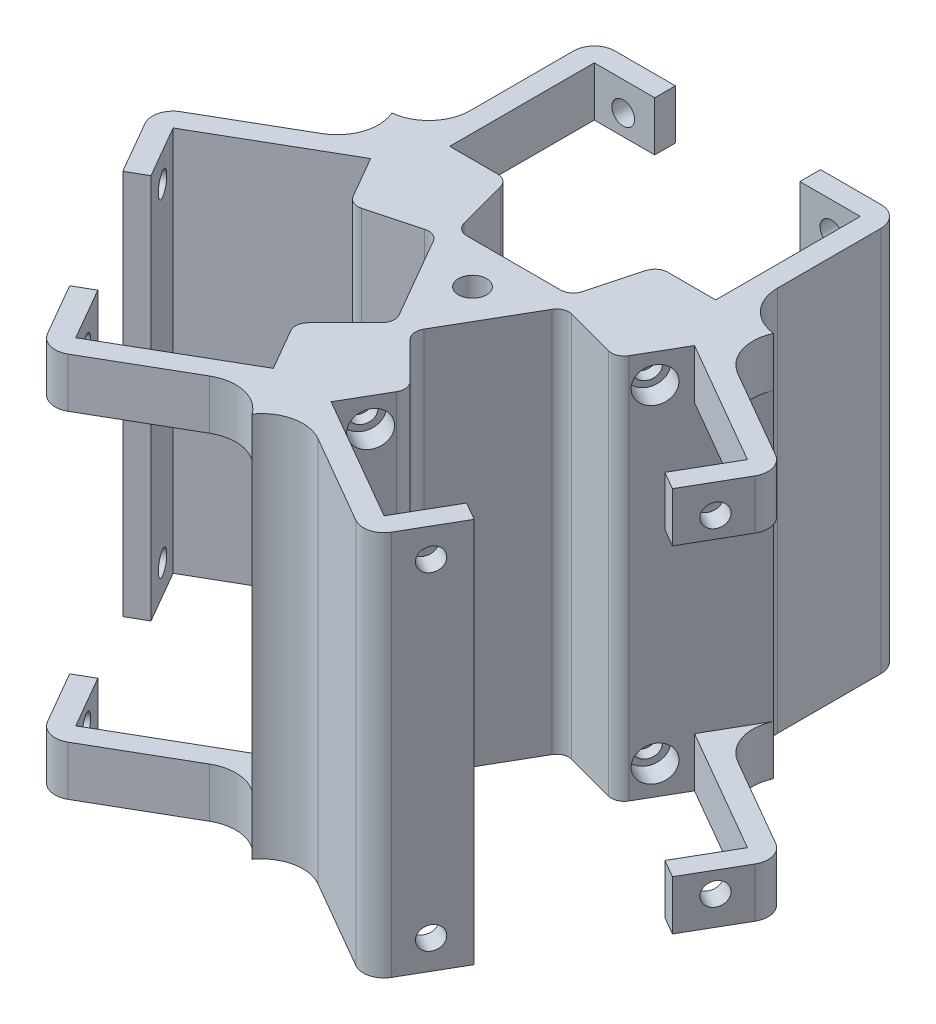
SolidWorks part; units mm, degrees
ref_plane "Alzado" through (0, 0, 0) normal (0, 0, 1) x (1, 0, 0)
ref_plane "Planta" through (0, 0, 0) normal (0, 1, 0) x (1, 0, 0)
ref_plane "Vista lateral" through (0, 0, 0) normal (1, 0, 0) x (0, 0, -1)
sketch "Croquis1" plane through (0, 0, 0) normal (0, 1, 0) x (1, 0, 0)
  line L0 (0, 50.8) -> (0, -50.8) construction
  line L1 (-50.8, 0) -> (50.8, 0) construction
  line L2 (0, 0) -> (-35.921, -35.921) construction
  line L3 (0, 0) -> (35.921, -35.921) construction
  line L10 (0, -17.5) -> (-15.1554, 8.75) construction
  line L11 (-15.1554, 8.75) -> (15.1554, 8.75) construction
  line L12 (15.1554, 8.75) -> (0, -17.5) construction
  line L13 (-1.2978, -16.7522) -> (-15.1813, 7.2027) construction
  line L14 (1.2978, -16.7522) -> (15.1813, 7.2027) construction
  line L15 (-13.8835, 9.4549) -> (13.8835, 9.4549) construction
  line L16 (1.6964, -16.0645) -> (13.335, -27.7031)
  line L17 (13.335, -27.7031) -> (0, -50.8)
  line L18 (0, -50.8) -> (-13.335, -27.7031)
  line L19 (-13.335, -27.7031) -> (-1.6964, -16.0645)
  line L20 (-17.3241, 25.4) -> (-13.0641, 9.5013)
  line L21 (-43.9941, 25.4) -> (-17.3241, 25.4)
  line L22 (-30.6591, 2.3031) -> (-43.9941, 25.4)
  line L23 (-14.7604, 6.5631) -> (-30.6591, 2.3031)
  line L24 (30.6591, 2.3031) -> (14.7604, 6.5631)
  line L25 (43.9941, 25.4) -> (30.6591, 2.3031)
  line L26 (17.3241, 25.4) -> (43.9941, 25.4)
  line L27 (13.0641, 9.5013) -> (17.3241, 25.4)
  line L28 (-14.7604, 6.5631) -> (-1.6964, -16.0645)
  line L29 (1.6964, -16.0645) -> (14.7604, 6.5631)
  line L30 (-13.0641, 9.5013) -> (13.0641, 9.5013)
  line L31 (-43.9941, 25.4) -> (0, -50.8) construction
  line L32 (43.9941, 25.4) -> (0, -50.8) construction
  line L33 (-43.9941, 25.4) -> (43.9941, 25.4) construction
  circle A0 centre (0, 0) radius 50.8 construction
  circle A7 centre (0, 0) radius 17.5 construction
  circle A8 centre (-13.8835, 7.9549) radius 1.5 construction
  circle A9 centre (13.8835, 7.9549) radius 1.5 construction
  circle A10 centre (0, -16) radius 1.5 construction
  arc A11 (-15.1813, 7.2027) -> (-13.8835, 9.4549) centre (-13.8835, 7.9549) cw construction
  arc A12 (15.1813, 7.2027) -> (13.8835, 9.4549) centre (13.8835, 7.9549) ccw construction
  arc A13 (1.2978, -16.7522) -> (-1.2978, -16.7522) centre (0, -16) cw construction
  arc A14 (-15.1813, 7.2027) -> (-13.8835, 9.4549) centre (-13.8835, 7.9549) cw construction
  arc A15 (13.8835, 9.4549) -> (15.1813, 7.2027) centre (13.8835, 7.9549) cw construction
  arc A16 (-1.2978, -16.7522) -> (1.2978, -16.7522) centre (0, -16) ccw construction
  circle A17 centre (0, 0) radius 76.2 construction
  point P45 (0, 0)
  dimension "D1" = 101.6
  dimension "D6" = 13.8835
  dimension "D9" = 3
  dimension "D5" = 3
  dimension "D4" = 35
  dimension "D10" = 152.4
  dimension "D2" = 45
  dimension "D3" = 45
  dimension "D7" = 26.67
extrude "Saliente-Extruir1" add sketch "Croquis1" along normal blind 88.9
sketch "Croquis4" plane through (0, 88.9, 0) normal (0, 1, 0) x (1, 0, 0)
  circle A0 centre (0, 0) radius 3.25
  dimension "D1" = 6.5
extrude "Cortar-Extruir1" cut sketch "Croquis4" against normal through all
fillet "Redondeo6" radius 3 5 edges at (-14.7604, 44.45, -6.5631) (1.6964, 44.45, 16.0645) (-1.6964, 44.45, 16.0645) (-13.0641, 44.45, -9.5013) (13.0641, 44.45, -9.5013)
fillet "Redondeo7" radius 3 6 edges at (-17.3241, 44.45, -25.4) (-30.6591, 44.45, -2.3031) (17.3241, 44.45, -25.4) (-13.335, 44.45, 27.7031) (30.6591, 44.45, -2.3031) (13.335, 44.45, 27.7031)
scale "Escala2" scale about centroid uniform scaling yes scale factor 1.05
sketch "Croquis9" plane through (0, 91.1225, 0) normal (0, 1, 0) x (1, 0, 0)
  line L9 (0, 76.2) -> (0, -76.2) construction
  line L10 (76.2, 0) -> (-76.2, 0) construction
  line L41 (-37.1934, 26.6702) -> (-37.1934, 61.6702)
  line L42 (-69.5041, -2.9545) -> (-39.1932, 14.5455)
  line L43 (-20.607, 26.6702) -> (-46.1934, 26.6702) construction
  line L44 (-32.1934, 66.6702) -> (-17.5643, 66.6702)
  line L45 (-17.5643, 66.6702) -> (-17.5643, 61.6702)
  line L46 (-17.5643, 61.6702) -> (-32.1934, 61.6702)
  line L47 (-32.1934, 61.6702) -> (-32.1934, 26.6702)
  line L48 (-32.1934, 26.6702) -> (-37.1934, 26.6702)
  line L49 (32.1934, 61.6702) -> (32.1934, 26.6702)
  line L50 (17.5643, 61.6702) -> (32.1934, 61.6702)
  line L51 (17.5643, 66.6702) -> (17.5643, 61.6702)
  line L52 (32.1934, 66.6702) -> (17.5643, 66.6702)
  line L53 (37.1934, 26.6702) -> (37.1934, 61.6702)
  line L54 (32.1934, 26.6702) -> (37.1934, 26.6702)
  line L55 (39.1937, 14.5452) -> (41.6937, 18.8753)
  line L56 (41.6937, 18.8753) -> (72.0046, 1.3753)
  line L57 (73.8347, -5.4548) -> (66.5202, -18.124)
  line L58 (66.5202, -18.124) -> (62.1901, -15.624)
  line L59 (62.1901, -15.624) -> (69.5046, -2.9548)
  line L60 (69.5046, -2.9548) -> (39.1937, 14.5452)
  line L61 (37.3112, -58.7154) -> (7.0003, -41.2154)
  line L62 (7.0003, -41.2154) -> (4.5003, -45.5455)
  line L63 (4.5003, -45.5455) -> (34.8112, -63.0455)
  line L64 (41.6414, -61.2154) -> (48.9559, -48.5462)
  line L65 (48.9559, -48.5462) -> (44.6258, -46.0462)
  line L66 (44.6258, -46.0462) -> (37.3112, -58.7154)
  line L79 (-39.1937, 14.5452) -> (-41.6937, 18.8753) [skipped]
  line L80 (-39.1932, 14.5455) -> (-41.6932, 18.8756)
  line L81 (-41.6937, 18.8753) -> (-72.0046, 1.3753) [skipped]
  line L83 (-41.6932, 18.8756) -> (-72.0041, 1.3756)
  line L85 (-69.5046, -2.9548) -> (-39.1937, 14.5452) [skipped]
  line L86 (-62.1901, -15.624) -> (-69.5046, -2.9548) [skipped]
  line L87 (-66.5202, -18.124) -> (-62.1901, -15.624) [skipped]
  line L88 (-73.8347, -5.4548) -> (-66.5202, -18.124) [skipped]
  line L89 (-73.8342, -5.4545) -> (-66.5197, -18.1237)
  line L90 (-66.5197, -18.1237) -> (-62.1896, -15.6237)
  line L91 (-62.1896, -15.6237) -> (-69.5041, -2.9545)
  line L92 (-46.1934, 26.6702) -> (-33.4002, 4.5117) construction
  line L93 (-7.0003, -41.2154) -> (-4.5003, -45.5455) [skipped]
  line L94 (-4.5003, -45.5455) -> (-34.8112, -63.0455) [skipped]
  line L95 (-41.6414, -61.2154) -> (-48.9559, -48.5462) [skipped]
  line L96 (-48.9559, -48.5462) -> (-44.6258, -46.0462) [skipped]
  line L97 (-44.6258, -46.0462) -> (-37.3112, -58.7154) [skipped]
  line L98 (-37.3112, -58.7154) -> (-7.0003, -41.2154) [skipped]
  line L99 (-6.9998, -41.2151) -> (-4.4998, -45.5452)
  line L100 (-4.4998, -45.5452) -> (-34.8107, -63.0452)
  line L101 (-41.6408, -61.2151) -> (-48.9554, -48.5459)
  line L102 (-48.9554, -48.5459) -> (-44.6253, -46.0459)
  line L103 (-44.6253, -46.0459) -> (-37.3107, -58.7151)
  line L104 (-37.3107, -58.7151) -> (-6.9998, -41.2151)
  line L105 (-12.7928, -31.1813) -> (0.0004, -53.3398) construction
  circle A0 centre (0, 0) radius 101.6 construction
  circle A1 centre (0, 0) radius 76.2 construction
  arc A8 (-37.1934, 61.6702) -> (-32.1934, 66.6702) centre (-32.1934, 61.6702) cw
  arc A9 (37.1934, 61.6702) -> (32.1934, 66.6702) centre (32.1934, 61.6702) ccw
  arc A10 (72.0046, 1.3753) -> (73.8347, -5.4548) centre (69.5046, -2.9548) cw
  arc A11 (34.8112, -63.0455) -> (41.6414, -61.2154) centre (37.3112, -58.7154) ccw
  arc A14 (-72.0046, 1.3753) -> (-73.8347, -5.4548) centre (-69.5046, -2.9548) ccw [skipped]
  arc A15 (-72.0041, 1.3756) -> (-73.8342, -5.4545) centre (-69.5041, -2.9545) ccw
  arc A16 (-34.8112, -63.0455) -> (-41.6414, -61.2154) centre (-37.3112, -58.7154) cw [skipped]
  arc A17 (-34.8107, -63.0452) -> (-41.6408, -61.2151) centre (-37.3107, -58.7151) cw
  point P55 (0.0002, 0.0003)
  point P56 (-1.3626, -0.7865)
  point P58 (0, 0)
  point P61 (0.0002, 0.0003)
  dimension "D1" = 152.4
  dimension "D2" = 203.2
  dimension "D3" = 5
  dimension "D9" = 2
  dimension "D4" = 9
  dimension "D5" = 35
  dimension "D6" = 3
  dimension "D7" = 2
sketch "Croquis12" plane through (0, 91.1225, 0) normal (0, 1, 0) x (1, 0, 0)
  line L0 (0, 101.6) -> (0, -101.6) construction
  circle A0 centre (0, 0) radius 76.2 construction
  circle A1 centre (0, 0) radius 101.6 construction
  dimension "D1" = 152.4
  dimension "D2" = 203.2
extrude "Saliente-Extruir2" add sketch "Croquis9" against normal through all
sketch "Croquis14" plane through (0, 0, -66.6702) normal (0, 0, -1) x (-1, 0, 0)
  line L0 (-32.1934, -2.2225) -> (-32.1934, 91.1225) construction
  line L1 (17.5643, 91.1225) -> (32.1934, 91.1225) construction
  circle A0 centre (25.1934, 84.1225) radius 2.75
  circle A1 centre (25.1934, 4.7775) radius 2.75
  circle A2 centre (-25.1934, 4.7775) radius 2.75
  circle A3 centre (-25.1934, 84.1225) radius 2.75
  dimension "D1" = 5.5
  dimension "D2" = 7
  dimension "D3" = 7
  dimension "D4" = 7
  dimension "D5" = 7
  dimension "D6" = 7
  dimension "D7" = 7
extrude "Cortar-Extruir2" cut sketch "Croquis14" against normal blind 10
sketch "Croquis15" plane through (0, 0, -26.6702) normal (0, 0, -1) x (-1, 0, 0)
  line L0 (32.1934, -2.2225) -> (32.1934, 91.1225) construction
  line L1 (-32.1934, -2.2225) -> (-20.6078, -2.2225) construction
  line L2 (-32.1934, 91.1225) -> (-20.6078, 91.1225) construction
  circle A0 centre (-25.1934, 4.7775) radius 4.25
  circle A1 centre (25.1934, 4.7775) radius 4.25
  circle A2 centre (-25.1934, 84.1225) radius 4.25
  circle A3 centre (25.1934, 84.1225) radius 4.25
  dimension "D1" = 8.5
  dimension "D2" = 7
  dimension "D3" = 7
  dimension "D4" = 7
  dimension "D5" = 7
  dimension "D6" = 7
  dimension "D7" = 7
extrude "Cortar-Extruir3" cut sketch "Croquis15" against normal blind 5.5
sketch "Croquis16" plane through (0, 0, -21.1702) normal (0, 0, -1) x (-1, 0, 0)
  circle A0 centre (-25.1934, 4.7775) radius 2.775
  circle A1 centre (25.1934, 4.7775) radius 2.775
  circle A2 centre (25.1934, 84.1225) radius 2.775
  circle A3 centre (-25.1934, 84.1225) radius 2.775
  dimension "D1" = 5.55
extrude "Cortar-Extruir4" cut sketch "Croquis16" against normal blind 3
pattern_circular "MatrizC7" count 3 over 360 about axis through (0.0004, -2.2225, -0.0002) along (0, 1, 0) of "Cortar-Extruir4", "Cortar-Extruir3"
sketch "Croquis17" plane through (18.5967, 0, -32.2104) normal (0.5, 0, -0.866) x (-0.866, 0, -0.5)
  line L0 (-26.6703, 91.1225) -> (-26.6703, -2.2225) construction
  line L1 (-26.6703, 79.1225) -> (-68.6703, 79.1225)
  line L2 (-26.6703, 79.1225) -> (-26.6703, 9.7775)
  line L3 (-26.6703, 9.7775) -> (-68.6703, 9.7775)
  line L4 (-68.6703, 79.1225) -> (-68.6703, 9.7775)
  line L5 (76.2, 91.1225) -> (-76.2, 91.1225) construction
  line L6 (-61.6702, -2.2225) -> (-26.6703, -2.2225) construction
  dimension "D1" = 42
  dimension "D2" = 12
  dimension "D3" = 12
extrude "Cortar-Extruir5" cut sketch "Croquis17" against normal blind 31
sketch "Croquis18" plane through (-37.1934, 0, 0) normal (-1, 0, 0) x (0, 0, 1)
  line L0 (-26.6702, 91.1225) -> (-26.6702, -2.2225) construction
  line L1 (-26.6702, 79.1225) -> (-71.6702, 79.1225)
  line L2 (-26.6702, 79.1225) -> (-26.6702, 9.7775)
  line L3 (-26.6702, 9.7775) -> (-71.6702, 9.7775)
  line L4 (-71.6702, 79.1225) -> (-71.6702, 9.7775)
  line L5 (101.6, 91.1225) -> (-101.6, 91.1225) construction
  line L6 (-61.6702, -2.2225) -> (-26.6702, -2.2225) construction
  dimension "D1" = 12
  dimension "D2" = 12
  dimension "D3" = 45
extrude "Cortar-Extruir6" cut sketch "Croquis18" against normal blind 31
fillet "Redondeo8" radius 10 2 edges at (-37.1934, 85.1225, -26.6702) (-37.1934, 3.7775, -26.6702)
fillet "Redondeo9" radius 10 1 edges at (37.1934, 44.45, -26.6702)
fillet "Redondeo12" radius 10 1 edges at (4.5004, 44.45, 45.5456)
fillet "Redondeo13" radius 10 2 edges at (41.6938, 85.1225, -18.8753) (41.6938, 3.7775, -18.8753)
pattern_circular "MatrizC8" count 3 over 360 about axis through (0.0004, 91.1225, -0.0002) along (0, 1, 0) of "Cortar-Extruir6"
fillet "Redondeo14" radius 10 2 edges at (-4.4998, 3.7775, 45.5452) (-4.4998, 85.1225, 45.5452)
fillet "Redondeo16" radius 10 1 edges at (-41.6932, 44.45, -18.8756)
fillet "Redondeo17" radius 3 1 edges at (15.4988, 44.45, -6.8915)
sketch "Croquis20" plane through (-57.7375, 0, 33.3348) normal (-0.866, 0, 0.5) x (0.5, 0, 0.866)
  line L0 (32.1934, -2.2225) -> (32.1934, 9.7775) construction
  line L1 (-87.9882, 91.1225) -> (87.9882, 91.1225) construction
  circle A0 centre (25.1934, 4.7775) radius 2.78
  circle A1 centre (25.1934, 84.1225) radius 2.78
  circle A2 centre (-25.1934, 84.1225) radius 2.78
  circle A3 centre (-25.1934, 4.7775) radius 2.78
  point P8 (0, 0)
  point P13 (0, 0)
  point P14 (0, 0)
  point P15 (0, 0)
  point P18 (0, 0)
  point P19 (0, 0)
  dimension "D1" = 5.56
  dimension "D2" = 7
  dimension "D3" = 7
  dimension "D4" = 7
  dimension "D5" = 7
extrude "Cortar-Extruir7" cut sketch "Croquis20" against normal blind 10
sketch "Croquis21" plane through (57.7381, 0, 33.3351) normal (0.866, 0, 0.5) x (0.5, 0, -0.866)
  line L0 (17.5643, 91.1225) -> (32.1934, 91.1225) construction
  line L1 (-32.1934, -2.2225) -> (-32.1934, 91.1225) construction
  line L2 (-32.1934, -2.2225) -> (-17.5643, -2.2225) construction
  circle A0 centre (25.1934, 4.7775) radius 2.775
  circle A1 centre (25.1934, 84.1225) radius 2.775
  circle A2 centre (-25.1934, 84.1225) radius 2.775
  circle A3 centre (-25.1934, 4.7775) radius 2.775
  point P11 (0, 0)
  point P14 (0, 0)
  point P17 (0, 0)
  point P18 (0, 0)
  dimension "D1" = 5.55
  dimension "D2" = 7
  dimension "D3" = 7
  dimension "D4" = 7
  dimension "D5" = 7
extrude "Cortar-Extruir8" cut sketch "Croquis21" against normal blind 10
